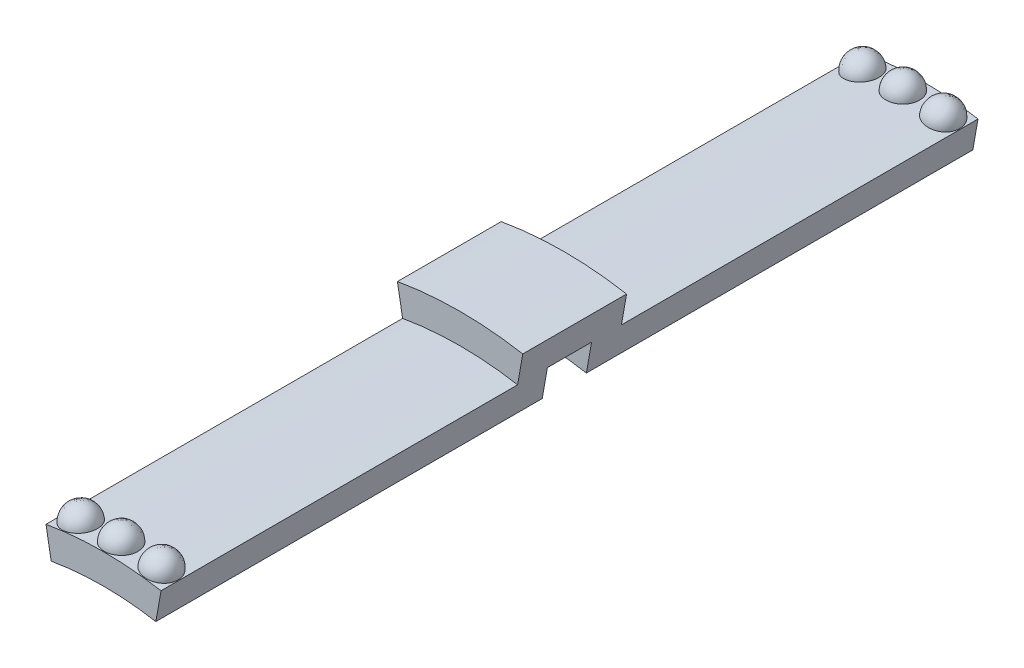
SolidWorks part; units mm, degrees
ref_plane "Front Plane" through (0, 0, 0) normal (0, 0, 1) x (1, 0, 0)
ref_plane "Top Plane" through (0, 0, 0) normal (0, 1, 0) x (1, 0, 0)
ref_plane "Right Plane" through (0, 0, 0) normal (1, 0, 0) x (0, 0, -1)
sketch "Sketch2" plane through (0, 0, 0) normal (1, 0, 0) x (0, 0, -1)
  line L0 (0, 0) -> (7.3757, 0) construction
  line L1 (0, 0) -> (0, 30) construction
  line L2 (0, 30) -> (2, 30)
  line L3 (2, 30) -> (2, 27.3)
  line L4 (2, 27.3) -> (37, 27.3)
  line L5 (37, 27.3) -> (37, 30)
  line L6 (0, 30) -> (0, 32.7)
  line L7 (0, 32.7) -> (4.7, 32.7)
  line L8 (4.7, 32.7) -> (4.7, 30)
  line L9 (4.7, 30) -> (37, 30)
  point P6 (11.3575, 0.5582)
  point P14 (11.3029, 0.5582)
  point P15 (11.2392, 0.5855)
  dimension "D1" = 2
  dimension "D2" = 2.7
  dimension "D3" = 2.7
  dimension "D4" = 2.7
  dimension "D5" = 35
  dimension "D6" = 30
revolve "Revolve1" add sketch "Sketch2" angle 20 mid plane about L0
ref_plane "Plane1" through (0, 0, -35.4) normal (0, 0, -1) x (-1, 0, 0)
sketch "Sketch3" plane through (0, 0, -35.4) normal (0, 0, -1) x (-1, 0, 0)
  line L0 (-1.4995, 29.9625) -> (1.4995, 29.9625)
  arc A0 (-5.2094, 29.5442) -> (5.2094, 29.5442) centre (0, 0) cw construction
  arc A1 (5.2094, 29.5442) -> (-5.2094, 29.5442) centre (0, 0) ccw construction
  arc A2 (-1.4995, 29.9625) -> (1.4995, 29.9625) centre (0, 30) cw
  dimension "D1" = 1.5
revolve "Revolve2" add sketch "Sketch3" angle 360 about L0
sketch "Sketch4" plane through (0, 0, 0) normal (0, 1, 0) x (1, 0, 0)
  line L0 (0, 0) -> (0, 14.6353) construction
pattern_circular "CirPattern1" count 2 every 7 about axis through (0, 0, 0) along (0, 0, -1) of "Revolve2" other way count 2
ref_plane "Plane2" through (0, 0, 0) normal (0, 0, 1) x (1, 0, 0)
mirror "Mirror2" about plane through (0, 0, 0) normal (0, 0, 1) of bodies 103
